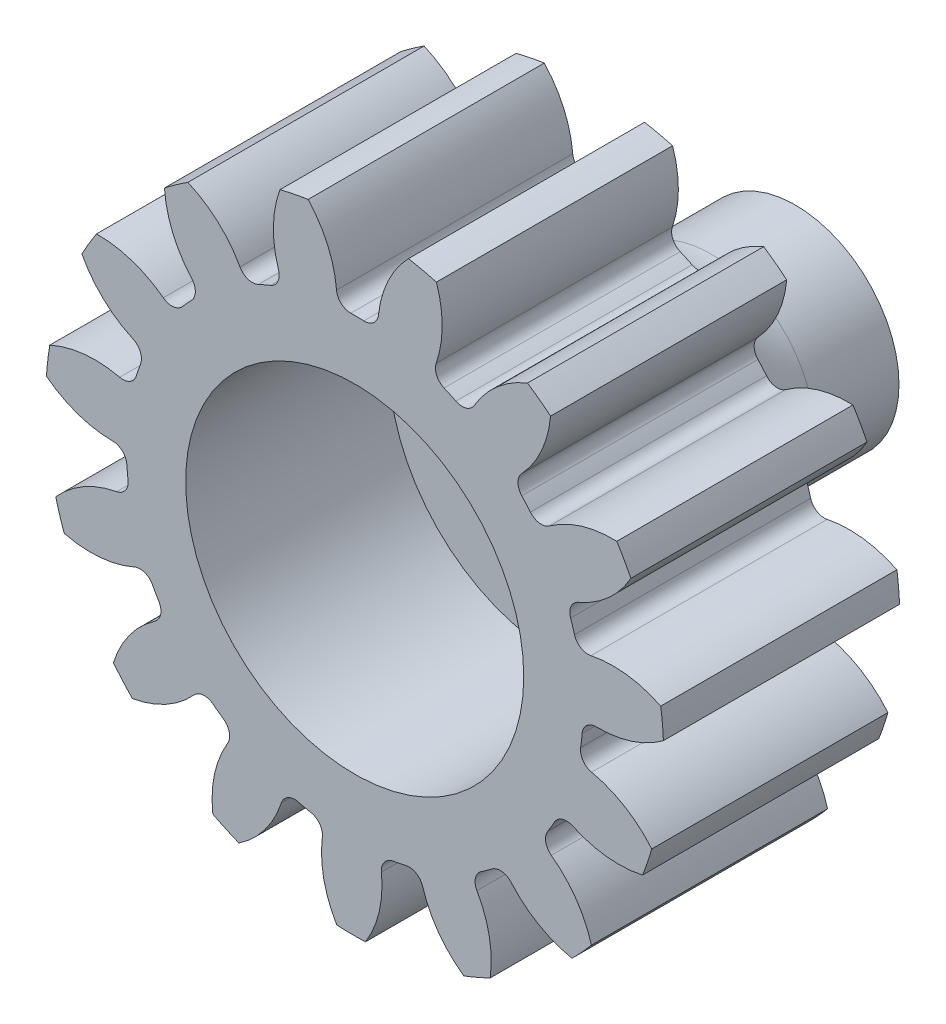
SolidWorks part; units mm, degrees
material "ABS"
ref_plane "Front" through (0, 0, 0) normal (0, 0, 1) x (1, 0, 0)
ref_plane "Top" through (0, 0, 0) normal (0, 1, 0) x (1, 0, 0)
ref_plane "Right" through (0, 0, 0) normal (1, 0, 0) x (0, 0, -1)
sketch "Sketch3" plane through (0, 0, 0) normal (0, 0, 1) x (1, 0, 0)
  circle A0 centre (0, 0) radius 21.59
  dimension "od" = 43.18
extrude "gearBody" add sketch "Sketch3" along normal blind 11
sketch "Sketch2" plane through (0, 0, 0) normal (0, 0, 1) x (1, 0, 0)
  line L0 (0, 0) -> (17.0393, 7.0579) construction
  line L1 (22.0105, -8.0941) -> (0, 0) construction
  line L2 (0, 0) -> (36.3143, 0) construction
  line L3 (19.0486, -0.229) -> (18.5878, -4.1711) construction
  line L5 (18.8182, -2.2) -> (0, 0) construction
  line L7 (0, 0) -> (18.4432, 0) construction
  arc A0 (18.4395, -0.3701) -> (18.0276, -3.8932) centre (0, 0) ccw construction
  arc A1 (21.5666, 1.0048) -> (20.7532, -5.9524) centre (0, 0) ccw construction
  arc A2 (19.0486, -0.229) -> (18.5878, -4.1711) centre (0, 0) ccw construction
  arc A3 (15.7838, -2.3046) -> (15.8898, -1.3984) centre (0, 0) ccw
  arc A4 (22.0105, -8.0941) -> (16.5506, -3.4102) centre (14.9518, -10.798) ccw
  arc A5 (22.0105, -8.0941) -> (23.2839, 2.7987) centre (0, 0) ccw
  arc A6 (23.2839, 2.7987) -> (16.8909, -0.4995) centre (17.0393, 7.0579) cw
  arc A7 (15.8898, -1.3984) -> (16.8909, -0.4995) centre (16.8715, -1.4848) cw
  arc A8 (16.5506, -3.4102) -> (15.7838, -2.3046) centre (16.759, -2.4469) cw
  point P6 (23.2839, 2.7987)
  point P22 (22.0105, -8.0941)
  dimension "baseDia" = 36.8864
  dimension "od" = 43.18
  dimension "pd" = 38.1
  dimension "rd" = 31.9024
  dimension "rFillet" = 0.9855
  dimension "pointX" = 23.2839
  dimension "pointY" = 2.7987
  dimension "CTT" = 3.9421
  dimension "flankCenterAngle" = 22.5
extrude "toothCut" cut sketch "Sketch2" along normal through all
pattern_circular "CirPattern1" count 15 over 360 about axis through (0, 0, 11) along (0, 0, -1) of "toothCut"
scale "Scale1" scale about centroid uniform scaling no x scale factor 0.666667 y scale factor 0.666667 z scale factor 1
sketch "hub1Dia" plane through (0, 0, 0) normal (0, 0, -1) x (-1, 0, 0)
  circle A0 centre (0, 0) radius 12.7
  dimension "hub1Dia" = 25.4
sketch "hub2Dia" plane through (0, 0, 11) normal (0, 0, 1) x (1, 0, 0)
  circle A0 centre (0, 0) radius 12.7
  dimension "hub2dia" = 25.4
sketch "boreDia" plane through (0, 0, 0) normal (0, 0, 1) x (1, 0, 0)
  circle A0 centre (0, 0) radius 7.874
  dimension "boreDia" = 15.748
extrude "bore" cut sketch "boreDia" against normal mid plane 25400
sketch "Sketch4" plane through (0, 0, 0) normal (1, 0, 0) x (0, 0, -1)
  line L0 (9.525, 0) -> (-1.524, 0)
  line L1 (-1.524, 0) -> (-1.524, 7.874)
  line L2 (-1.524, 7.874) -> (0, 7.874)
  line L3 (0, 8.1454) -> (0, 11.133) construction
  line L4 (0, 7.874) -> (0, 10.414)
  line L7 (5.588, 4.826) -> (9.525, 4.826)
  line L8 (9.525, 4.826) -> (9.525, 0)
  line L9 (0, 0) -> (18.4907, 0) construction
  arc A0 (0, 10.414) -> (5.588, 4.826) centre (5.588, 10.414) ccw
  dimension "D2" = 5.588
  dimension "D1" = 15.748
  dimension "D3" = 1.524
  dimension "D5" = 9.652
  dimension "D6" = 9.525
revolve "Revolve1" add sketch "Sketch4" angle 360 about L9
sketch "Sketch5" plane through (0, 0, -9.525) normal (0, 0, -1) x (-1, 0, 0)
  circle A0 centre (0, 0) radius 4.1
  dimension "D1" = 8.2
extrude "Cut-Extrude1" cut sketch "Sketch5" against normal blind 5.3
equation "\"Motor_OD\" = 54.4mm"
equation "\"Motor_Length\" = 401mm"
equation "\"Aft_Section_Length\" = 32in"
equation "\"Mid_Coupler_Length\" = 12in"
equation "\"AB_Coupler_OD_Length\"= 1in"
equation "\"AB_Coupling_Section_Length\"= 0.375in"
equation "\"AB_Coupler_Length\"= \"AB_Coupler_OD_Length\" + \"AB_Coupling_Section_Length\" * 2"
equation "\"Cutout_Angle\" = 60"
equation "\"AB_Paddle_Height\" = 0.375in"
equation "\"AB_Coupler_Num_Screws\"= 4"
equation "\"Num_Cutouts\" = 4"
equation "\"AB_Coupler_OD\"= 4.024in"
equation "\"AB_Coupler_ID\"= 3.7in"
equation "\"AB_Coupler_Surface_Diameter\"= 3.899in"
equation "\"AB_Coupling_Screw_Diameter\"= 4.5mm"
equation "\"AB_Central_Bushing_Length\" = 0.75in"
equation "\"Lead_Screw_Dist\" = 2in"
equation "\"Lead_Screw_Diam\" = 0.375in"
equation "\"Lead_Screw_Length\" = \"Mid_Coupler_Length\" + 2*0.375in + 2*0.5in"
equation "\"Paddle_Pin_Offset\" = 0.25in"
equation "\"Paddle_Pin_Radius\" = 2.25*2/3in"
equation "\"Paddle_Gear_OD\" = 3.2in"
equation "\"Fwd_BKHD_From_Top\" = 18in"
equation "\"Body_Tube_OD\"= 4.024in"
equation "\"Body_Tube_ID\"= 3.90in"
equation "\"Coupler_OD\" = 3.899in"
equation "\"Coupler_ID\" = 3.755in"
equation "\"Fwd_Section_Length\" = 20in"
equation "\"Mid_Section_Length\" = 4in"
equation "\"Aft_Upper_Tube_Length\" = 10in"
equation "\"Aft_Lower_Tube_Length\" = 18in"
equation "\"Nosecone_Coupler_Length\" = 5in"
equation "\"Avionics_Bulkhead_Thickness\" = 0.25in"
equation "\"Avionics_Bulkhead_Lip\" = 0.125in"
equation "\"Avionics_Board_Length\" = \"Mid_Coupler_Length\" - 2*\"Avionics_Bulkhead_Lip\""
equation "\"Lead_Screw_Hole_Diam\" = 0.386in"
equation "\"Centering_Ring_Cutout_Dia\"= 1in"
equation "\"Fin_Thickness\" = 0.118in"
equation "\"Airbrakes_Wire_Hole_Dist\" = 1.1*2/3in"
equation "\"Airbrakes_Wire_Hole_Dia\" = 0.25in"
equation "\"Drive_Gear_OD\" = 1.7*2/3in"
equation "\"DB9_Hole_Dist\" = 25mm"
equation "\"DB9_Relief_Width\" = 0.47in"
equation "\"DB9_Relief_Hole_Offset\" = 0.09in"
equation "\"Servo_Gear_Offset\" = 0.5in"
equation "\"Mounting_Bracket_Centerhole_DIA\" = 0.4in"
equation "\"Drive_Gear_Shaft_DIA\" = \"Mounting_Bracket_Centerhole_DIA\" - 0.02in"
equation "\"Drive_Gear_Fillet\" = 0.22in"
equation "\"Drive_Gear_ID\" = 0.62in"
equation "\"M3_Thread_Clearance\" = 3.8mm"
equation "\"M3_Screw_Head_Diam\" = 6.5mm"
equation "\"Screw_Angle\" = 12.5deg"
equation "\"M3_Insert_OD\" = 4.1mm"
equation "\"M4_Insert_OD\" = 5.5mm"
equation "\"Mounting_Hole_Dist\" = 0.15in"
equation "\"Cam_Slot_Length\" = 7mm"
equation "\"Cam_Slot_Width\" = 10mm"
equation "\"D2@Sketch4\"=\"Drive_Gear_Fillet\""
equation "\"D5@Sketch4\"=\"Drive_Gear_Shaft_DIA\""
equation "\"D1@Sketch4\"=\"Drive_Gear_ID\""
equation "\"Drive_Gear_Offset\" = 0.01in"
